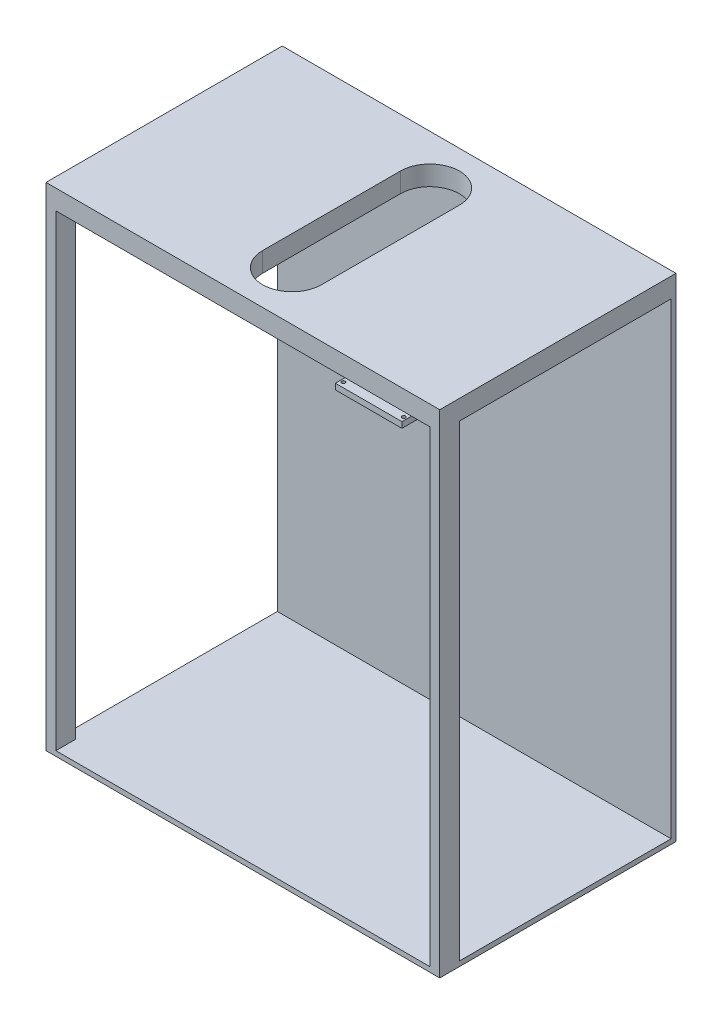
SolidWorks part; units mm, degrees
ref_plane "Front Plane" through (0, 0, 0) normal (0, 0, 1) x (1, 0, 0)
ref_plane "Top Plane" through (0, 0, 0) normal (0, 1, 0) x (1, 0, 0)
ref_plane "Right Plane" through (0, 0, 0) normal (1, 0, 0) x (0, 0, -1)
sketch "Sketch1" plane through (0, 0, 0) normal (0, 0, 1) x (1, 0, 0)
  line L1 (0, 0) -> (508, 0)
  line L2 (0, 0) -> (0, 635)
  line L3 (0, 635) -> (508, 635)
  line L4 (508, 0) -> (508, 635)
  dimension "D1" = 635
  dimension "D2" = 508
extrude "Boss-Extrude1" add sketch "Sketch1" along normal blind 6.35
sketch "Sketch3" plane through (0, 0, 0) normal (0, 1, 0) x (1, 0, 0)
  line L1 (0, -6.35) -> (508, -6.35)
  line L2 (0, -6.35) -> (0, -304.8)
  line L3 (0, -304.8) -> (508, -304.8)
  line L4 (508, -6.35) -> (508, -304.8)
  point P5 (0, 0)
  dimension "D1" = 298.45
extrude "Boss-Extrude3" add sketch "Sketch3" along normal blind 6.35
sketch "Sketch4" plane through (0, 0, 0) normal (1, 0, 0) x (0, 0, -1)
  line L0 (-304.8, 6.35) -> (-304.8, 635)
  line L1 (-304.8, 635) -> (-6.35, 635)
  line L2 (-6.35, 635) -> (-6.35, 609.6)
  line L4 (-304.8, 6.35) -> (-6.35, 6.35) construction
  line L6 (-6.35, 609.6) -> (-279.4, 609.6)
  line L7 (-6.35, 635) -> (-6.35, 6.35) construction
  line L8 (-279.4, 609.6) -> (-279.4, 6.35)
  line L9 (-279.4, 6.35) -> (-304.8, 6.35)
  dimension "D1" = 25.4
  dimension "D2" = 25.4
extrude "Boss-Extrude4" add sketch "Sketch4" along normal blind 12.7
sketch "Sketch5" plane through (0, 0, 0) normal (0, 0, 1) x (1, 0, 0)
  line L0 (254, 635) -> (254, 0) construction
  line L6 (0, 0) -> (508, 0) construction
  line L7 (508, 635) -> (0, 635) construction
  point P6 (254, 635)
  point P9 (254, 0)
ref_plane "Plane1" through (254, 0, 0) normal (1, 0, 0) x (0, 0, -1)
mirror "Mirror1" about plane through (254, 0, 0) normal (1, 0, 0) of "Boss-Extrude4"
ref_plane "Plane2" through (12.7, 0, 0) normal (1, 0, 0) x (0, 0, -1)
sketch "Sketch6" plane through (12.7, 0, 0) normal (1, 0, 0) x (0, 0, -1)
  line L1 (-304.8, 635) -> (-6.35, 635)
  line L2 (-304.8, 635) -> (-304.8, 609.6)
  line L3 (-304.8, 609.6) -> (-6.35, 609.6)
  line L4 (-6.35, 635) -> (-6.35, 609.6)
extrude "Boss-Extrude6" add sketch "Sketch6" along normal up to surface (482.6 mm away) up to face at (495.3, 416.9833, 196.85)
ref_plane "Plane3" through (0, 635, 0) normal (0, 1, 0) x (1, 0, 0)
sketch "Sketch7" plane through (0, 635, 0) normal (0, 1, 0) x (1, 0, 0)
  line L0 (508, 0) -> (0, 0) construction
  line L1 (254, 0) -> (254, -304.8) construction
  line L2 (508, -304.8) -> (0, -304.8) construction
  line L3 (0, -152.4) -> (508, -152.4) construction
  line L4 (0, -304.8) -> (0, 0) construction
  line L5 (508, -304.8) -> (508, 0) construction
  line L6 (254, -63.5) -> (254, -241.3) construction
  line L7 (292.1, -63.5) -> (292.1, -241.3)
  line L8 (215.9, -63.5) -> (215.9, -241.3)
  arc A1 (292.1, -63.5) -> (215.9, -63.5) centre (254, -63.5) ccw
  arc A2 (215.9, -241.3) -> (292.1, -241.3) centre (254, -241.3) ccw
  point P15 (254, -152.4)
  dimension "D1" = 76.2
  dimension "D2" = 177.8
extrude "Cut-Extrude1" cut sketch "Sketch7" against normal up to surface (25.4 mm away) up to face at (254, 609.6, 217.4875)
ref_plane "Plane4" through (254, 0, 0) normal (1, 0, 0) x (0, 0, -1)
sketch "Sketch8" plane through (254, 0, 0) normal (1, 0, 0) x (0, 0, -1)
  line L0 (-6.35, 6.35) -> (-6.35, 609.6) construction
  line L5 (-304.8, 635) -> (0, 635) construction
  line L6 (-6.35, 471.25) -> (-106.35, 471.25) construction
  line L7 (-6.35, 337.5) -> (-106.35, 337.5) construction
  line L8 (-6.35, 435) -> (-106.35, 435) construction
  line L9 (-6.35, 427.5) -> (-106.35, 427.5) construction
  line L10 (-56.35, 427.5) -> (-6.35, 407.5)
  line L11 (-6.35, 407.5) -> (-6.35, 427.5)
  line L12 (-6.35, 427.5) -> (-56.35, 427.5)
  point P12 (0, 0)
  dimension "D1" = 36.25
  dimension "D2" = 90
  dimension "D3" = 200
  dimension "D4" = 7.5
  dimension "D5" = 50
  dimension "D6" = 20
ref_plane "Plane5" through (0, 435, 0) normal (0, 1, 0) x (1, 0, 0)
sketch "Sketch9" plane through (0, 435, 0) normal (0, 1, 0) x (1, 0, 0)
  line L4 (211.0837, -6.35) -> (296.9163, -142.4981) construction
  line L5 (211.0837, -142.4981) -> (296.9163, -6.35) construction
  line L6 (254, -167.64) -> (254, 167.64) construction
  line L7 (211.0837, -142.4981) -> (296.9163, -142.4981)
  line L8 (211.0837, -142.4981) -> (211.0837, -6.35)
  line L9 (211.0837, -6.35) -> (296.9163, -6.35)
  line L10 (296.9163, -142.4981) -> (296.9163, -6.35)
  line L11 (508, -6.35) -> (0, -6.35) construction
  circle A0 centre (292.9165, -136.1537) radius 2.25
  circle A1 centre (292.9165, -12.6944) radius 2.25
  circle A2 centre (215.0835, -12.6944) radius 2.25
  circle A3 centre (215.0835, -136.1537) radius 2.25
  point P2 (254, -6.35)
  dimension "D3" = 4.5
  dimension "D4" = 4.5
  dimension "D5" = 4.5
  dimension "D6" = 4.5
  dimension "D1" = 136.1481
  dimension "D2" = 85.8325
  dimension "D7" = 7.5
  dimension "D8" = 7.5
  dimension "D9" = 7.5
  dimension "D10" = 7.5
extrude "Boss-Extrude7" add sketch "Sketch9" against normal blind 7.5
extrude "Boss-Extrude8" add sketch "Sketch8" along normal mid plane 70
